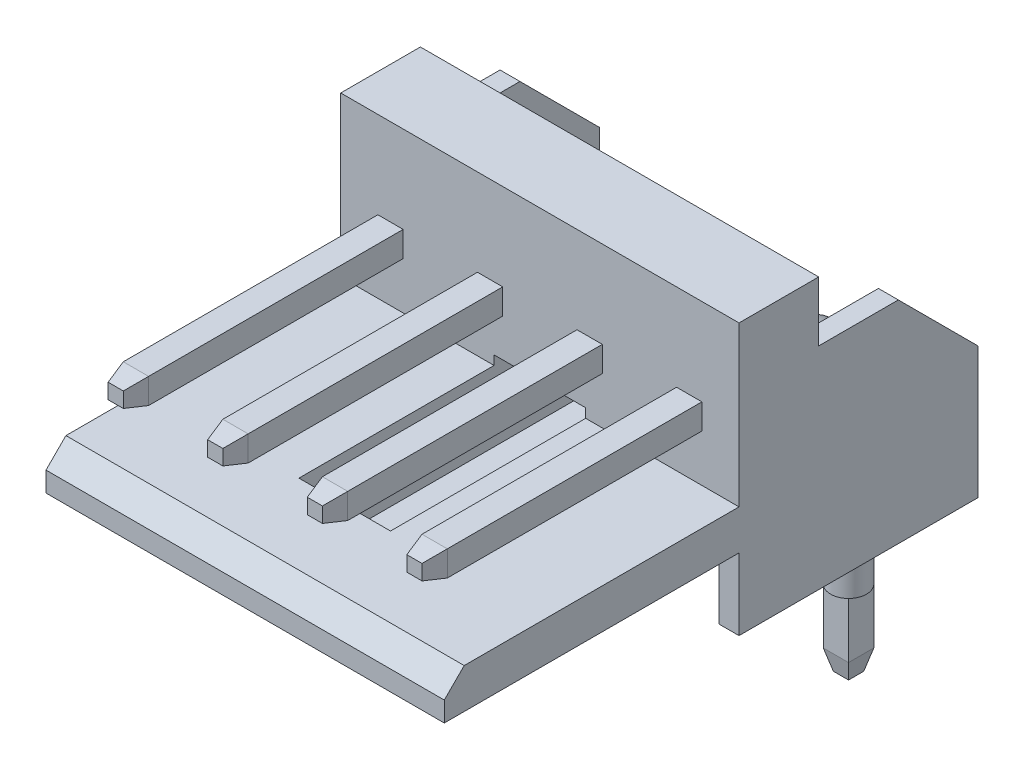
SolidWorks part; units mm, degrees
ref_plane "Front Plane" through (0, 0, 0) normal (0, 0, 1) x (1, 0, 0)
ref_plane "Top Plane" through (0, 0, 0) normal (0, 1, 0) x (1, 0, 0)
ref_plane "Right Plane" through (0, 0, 0) normal (1, 0, 0) x (0, 0, -1)
sketch "Sketch1" plane through (0, 0, 0) normal (0, 0, 1) x (1, 0, 0)
  line L0 (-5, 0) -> (5, 0)
  line L1 (-5, 4) -> (5, 4)
  line L3 (5, 0) -> (5, 4)
  line L5 (-5, 4) -> (-5, 0)
  dimension "D1" = 10
  dimension "D2" = 5
  dimension "D3" = 4
extrude "Body base" add sketch "Sketch1" against normal blind 2
sketch "Sketch2" plane through (0, 0, 0) normal (0, 0, 1) x (1, 0, 0)
  line L0 (3.4325, 1.1825) -> (4.0675, 1.8175) construction
  line L1 (-4.0675, 1.8175) -> (-3.4325, 1.8175)
  line L2 (-4.0675, 1.8175) -> (-4.0675, 1.1825)
  line L3 (-4.0675, 1.1825) -> (-3.4325, 1.1825)
  line L4 (-3.4325, 1.8175) -> (-3.4325, 1.1825)
  line L5 (-1.5675, 1.8175) -> (-0.9325, 1.8175)
  line L6 (-1.5675, 1.8175) -> (-1.5675, 1.1825)
  line L7 (-1.5675, 1.1825) -> (-0.9325, 1.1825)
  line L8 (-0.9325, 1.8175) -> (-0.9325, 1.1825)
  line L9 (0.9325, 1.8175) -> (1.5675, 1.8175)
  line L10 (0.9325, 1.8175) -> (0.9325, 1.1825)
  line L11 (0.9325, 1.1825) -> (1.5675, 1.1825)
  line L12 (1.5675, 1.8175) -> (1.5675, 1.1825)
  line L13 (3.4325, 1.8175) -> (4.0675, 1.8175)
  line L14 (3.4325, 1.8175) -> (3.4325, 1.1825)
  line L15 (3.4325, 1.1825) -> (4.0675, 1.1825)
  line L16 (4.0675, 1.8175) -> (4.0675, 1.1825)
  line L17 (0.9325, 1.1825) -> (1.5675, 1.8175) construction
  line L18 (-0.9325, 1.1825) -> (-1.5675, 1.8175) construction
  line L19 (-3.4325, 1.1825) -> (-4.0675, 1.8175) construction
  line L20 (-5, 0) -> (5, 0) construction
  point P16 (3.75, 1.5)
  point P17 (1.25, 1.5)
  point P18 (-1.25, 1.5)
  point P19 (-3.75, 1.5)
  dimension "D1" = 0.635
  dimension "D2" = 1.25
  dimension "D3" = 2.5
  dimension "D4" = 2.5
  dimension "D5" = 2.5
  dimension "D6" = 1.5
extrude "Horizontal pins" add sketch "Sketch2" along normal blind 6.9
sketch "Sketch3" plane through (0, 0, 0) normal (0, -1, 0) x (1, 0, 0)
  line L0 (-5, -2) -> (-5, 0) construction
  line L1 (-5, -2) -> (-5, 7.4)
  line L2 (5, -2) -> (-5, -2) construction
  line L3 (5, -2) -> (-5, -2)
  line L4 (5, -2) -> (5, 0) construction
  line L5 (5, -2) -> (5, 7.4)
  line L6 (-5, 7.4) -> (5, 7.4)
  line L7 (5, 0) -> (-5, 0) construction
  dimension "D1" = 7.4
extrude "Body - horizontal shelf" add sketch "Sketch3" along normal blind 1
chamfer "Mating connector lead-in chamfer" distance 0.5 1 edges at (0, 0, 7.4)
sketch "Sketch4" plane through (0, 4, 0) normal (0, 1, 0) x (1, 0, 0)
  line L0 (-5, 0) -> (-5, 6)
  line L1 (-5, 6) -> (-4.5, 6)
  line L2 (-4.5, 6) -> (-4.5, 0)
  line L4 (4.5, 6) -> (4.5, 0)
  line L5 (4.5, 6) -> (5, 6)
  line L6 (5, 6) -> (5, 0)
  line L7 (5, 0) -> (-5, 0) construction
  line L8 (5, 0) -> (4.5, 0)
  line L9 (-4.5, 0) -> (-5, 0)
  dimension "D1" = 0.5
  dimension "D2" = 6
extrude "Body sidewalls" add sketch "Sketch4" against normal blind 6.8
sketch "Sketch5" plane through (0, 0, 0) normal (1, 0, 0) x (0, 0, -1)
  line L0 (2, 4) -> (2, 2.5)
  line L1 (2, 2.5) -> (4, 2.5)
  line L2 (4, 2.5) -> (6, 0.5)
  line L3 (6, -2.8) -> (6, 4) construction
  line L4 (6, 0.5) -> (6, 4)
  line L5 (6, 4) -> (2, 4)
  dimension "D1" = 1.5
  dimension "D2" = 135
  dimension "D3" = 2
extrude "Body sidewall - materia removall" cut sketch "Sketch5" against normal mid plane 14.42
sketch "Sketch6" plane through (0, 0, -2) normal (0, 0, -1) x (-1, 0, 0)
  line L0 (-2, -1) -> (-1.2668, -2.27)
  line L1 (4.5, -1) -> (-4.5, -1) construction
  line L2 (-1.2668, -2.27) -> (1.2668, -2.27)
  line L3 (1.2668, -2.27) -> (2, -1)
  line L4 (2, -1) -> (-2, -1)
  point P4 (0, -1)
  dimension "D1" = 4
  dimension "D2" = 60
  dimension "D3" = 60
  dimension "D4" = 1.27
extrude "Locking trough - exterior" add sketch "Sketch6" against normal blind 7
chamfer "Locking trough chamfer - exterior" distance 1.27 angle 45 1 edges at (0, -2.27, 5)
sketch "Sketch8" plane through (0, 0, 0) normal (1, 0, 0) x (0, 0, -1)
  line L0 (-4.9, 0) -> (-3.13, -1.77)
  line L1 (0, 0) -> (-6.9, 0) construction
  line L2 (-3.13, -1.77) -> (6, -1.77)
  line L3 (6, -2.8) -> (6, 0.5) construction
  line L4 (6, -1.77) -> (6, 0.23)
  line L5 (6, 0.23) -> (0, 0.23)
  line L6 (0, 0) -> (0, 4) construction
  line L7 (0, 0) -> (0, 0.23)
  line L8 (0, 0) -> (-4.9, 0)
  line L9 (-7.4, -1) -> (-7.4, -0.5) construction
  line L10 (-5, -1) -> (-3.73, -2.27) construction
  line L11 (-3.73, -2.27) -> (2, -2.27) construction
  dimension "D1" = 2.5
  dimension "D2" = 0.5
  dimension "D3" = 2
extrude "Locking trough - material removal" cut sketch "Sketch8" against normal mid plane 2.3
sketch "Sketch9" plane through (4.0675, 0, 0) normal (1, 0, 0) x (0, 0, -1)
  line L0 (2, 1.8175) -> (2.8175, 1.8175)
  line L1 (4.3175, 0.3175) -> (4.3175, -6.2)
  line L2 (4.3175, -6.2) -> (3.6825, -6.2)
  line L3 (3.6825, -6.2) -> (3.6825, 0.3175)
  line L4 (2, 1.8175) -> (2, 1.1825)
  line L5 (2.8175, 1.1825) -> (2, 1.1825)
  line L6 (-6.9, 1.8175) -> (0, 1.8175) construction
  line L7 (0, -2.8) -> (6, -2.8) construction
  line L8 (6, -2.8) -> (6, 0.5) construction
  line L9 (2, 4) -> (2, 2.5) construction
  arc A0 (2.8175, 1.8175) -> (4.3175, 0.3175) centre (2.8175, 0.3175) cw
  arc A1 (3.6825, 0.3175) -> (2.8175, 1.1825) centre (2.8175, 0.3175) ccw
  point P14 (4, -6.2)
  dimension "D3" = 1.5
  dimension "D1" = 0.635
  dimension "D2" = 2
  dimension "D4" = 3.4
extrude "Remainder of pin" add sketch "Sketch9" against normal blind 0.635
pattern_linear "LPattern - complement  of pins" count 4 spacing 2.5 along (-1, 0, 0) of "Remainder of pin"
chamfer "Pin chamfer1" distance 0.508 distance2 0.127 16 edges at (3.4325, 1.5, 6.9) (3.75, 1.1825, 6.9) (4.0675, 1.5, 6.9) (3.75, 1.8175, 6.9) (0.9325, 1.5, 6.9) (1.25, 1.1825, 6.9) (1.5675, 1.5, 6.9) (1.25, 1.8175, 6.9) (-1.5675, 1.5, 6.9) (-1.25, 1.1825, 6.9) (-0.9325, 1.5, 6.9) (-1.25, 1.8175, 6.9) (-4.0675, 1.5, 6.9) (-3.75, 1.1825, 6.9) (-3.4325, 1.5, 6.9) (-3.75, 1.8175, 6.9) first distance on face at (3.4325, 1.5, 3.45) first distance on face at (3.75, 1.1825, 3.45) first distance on face at (4.0675, 1.5, 3.45) first distance on face at (3.75, 1.8175, 3.45) first distance on face at (0.9325, 1.5, 3.45) first distance on face at (1.25, 1.1825, 3.45) first distance on face at (1.5675, 1.5, 3.45) first distance on face at (1.25, 1.8175, 3.45) first distance on face at (-1.5675, 1.5, 3.45) first distance on face at (-1.25, 1.1825, 3.45) first distance on face at (-0.9325, 1.5, 3.45) first distance on face at (-1.25, 1.8175, 3.45) first distance on face at (-4.0675, 1.5, 3.45) first distance on face at (-3.75, 1.1825, 3.45) first distance on face at (-3.4325, 1.5, 3.45) first distance on face at (-3.75, 1.8175, 3.45)
chamfer "Pin chamfer2" distance 0.127 distance2 0.508 16 edges at (-4.0675, -6.2, -4) (-3.75, -6.2, -3.6825) (-3.75, -6.2, -4.3175) (-3.4325, -6.2, -4) (-1.5675, -6.2, -4) (-1.25, -6.2, -4.3175) (-1.25, -6.2, -3.6825) (-0.9325, -6.2, -4) (0.9325, -6.2, -4) (1.25, -6.2, -3.6825) (1.25, -6.2, -4.3175) (1.5675, -6.2, -4) (3.75, -6.2, -4.3175) (3.4325, -6.2, -4) (3.75, -6.2, -3.6825) (4.0675, -6.2, -4) first distance on face at (-3.75, -6.2, -4) first distance on face at (-1.25, -6.2, -4) first distance on face at (1.25, -6.2, -4) first distance on face at (3.75, -6.2, -4)
sketch "Sketch11" plane through (0, -2.8, 0) normal (0, -1, 0) x (1, 0, 0)
  line L0 (3.4325, -4.3175) -> (4.0675, -3.6825) construction
  circle A0 centre (3.75, -4) radius 0.449
  point P4 (3.75, -4)
extrude "Pin 1 marking and mate aide" add sketch "Sketch11" along normal blind 1.5
